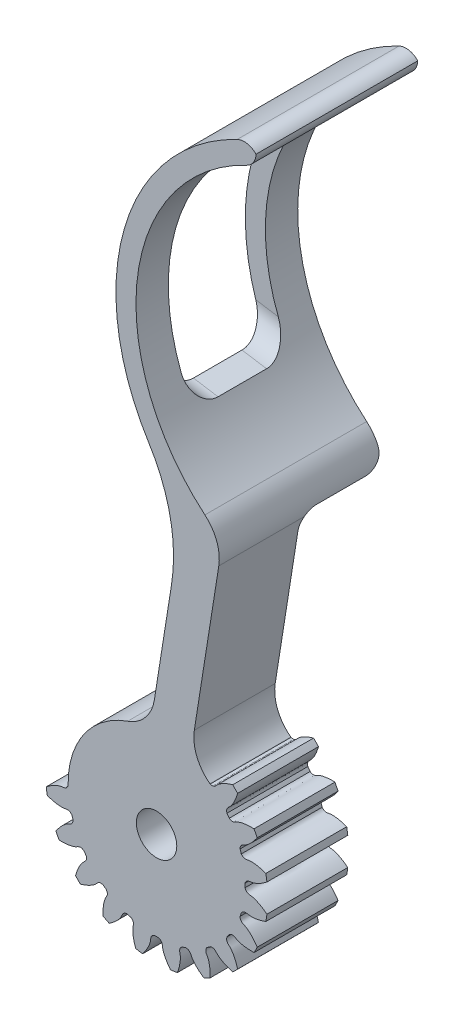
SolidWorks part; units mm, degrees
material "聚脂树脂"
ref_plane "前视基准面" through (0, 0, 0) normal (0, 0, 1) x (1, 0, 0)
ref_plane "上视基准面" through (0, 0, 0) normal (0, 1, 0) x (1, 0, 0)
ref_plane "右视基准面" through (0, 0, 0) normal (1, 0, 0) x (0, 0, -1)
other "Configuration Table"
sketch "草图1" plane through (0, 0, 0) normal (0, 0, 1) x (1, 0, 0)
  circle A0 centre (0, 0) radius 13.75
extrude "凸台-拉伸1" add sketch "草图1" along normal blind 10
ref_axis "基准轴1" through (0, 0, -1.5) along (0, 0, 1)
sketch "草图2" plane through (0, 0, 0) normal (0, 0, 1) x (1, 0, 0)
  line L0 (0, 0) -> (0, 13.75) construction
  circle A0 centre (0, 0) radius 13.75 construction
  arc A1 (0.2416, 10.9348) -> (-0.2416, 10.9348) centre (0, 0) ccw
  arc A2 (3.9764, 15.6228) -> (-3.9764, 15.6228) centre (0, 0) ccw
  spline S0 degree 3 poles (0.2416, 10.9348) (0.764, 11.1168) (0.6964, 11.4839) (0.7661, 11.8375) (0.7736, 11.8719) (0.7829, 11.9108) (0.7941, 11.954) (0.8075, 12.0015) (0.8231, 12.0532) (0.8413, 12.1091) (0.8621, 12.169) (0.8857, 12.2329) (0.9123, 12.3007) (0.9421, 12.3723) (0.9752, 12.4476) (1.0117, 12.5264) (1.0519, 12.6088) (1.0959, 12.6945) (1.1438, 12.7834) (1.1957, 12.8755) (1.2519, 12.9705) (1.3125, 13.0684) (1.3775, 13.1691) (1.4472, 13.2723) (1.5216, 13.3779) (1.601, 13.4858) (1.6853, 13.5958) (1.7747, 13.7078) (1.8694, 13.8216) (1.9693, 13.937) (2.0748, 14.0539) (2.1857, 14.1721) (2.3023, 14.2914) (2.4246, 14.4116) (2.5527, 14.5326) (2.6866, 14.6542) (2.8265, 14.7761) (2.9725, 14.8983) (3.1245, 15.0204) (3.2826, 15.1424) (3.4469, 15.2639) (3.6768, 15.427) (3.8549, 15.5454) (3.9764, 15.6228) knots 0 0 0 0 0.165916 0.170906 0.176664 0.183189 0.190482 0.198542 0.207371 0.216967 0.22733 0.238462 0.250361 0.263027 0.276462 0.290664 0.305634 0.321371 0.337876 0.355149 0.37319 0.391998 0.411574 0.431917 0.453028 0.474907 0.497554 0.520968 0.54515 0.570099 0.595817 0.622302 0.649554 0.677575 0.706363 0.735918 0.766242 0.797333 0.829191 0.861818 0.895212 0.929373 1 1 1 1
  spline S1 degree 3 poles (-0.2416, 10.9348) (-0.764, 11.1168) (-0.6964, 11.4839) (-0.7661, 11.8375) (-0.7736, 11.8719) (-0.7829, 11.9108) (-0.7941, 11.954) (-0.8075, 12.0015) (-0.8231, 12.0532) (-0.8413, 12.1091) (-0.8621, 12.169) (-0.8857, 12.2329) (-0.9123, 12.3007) (-0.9421, 12.3723) (-0.9752, 12.4476) (-1.0117, 12.5264) (-1.0519, 12.6088) (-1.0959, 12.6945) (-1.1438, 12.7834) (-1.1957, 12.8755) (-1.2519, 12.9705) (-1.3125, 13.0684) (-1.3775, 13.1691) (-1.4472, 13.2723) (-1.5216, 13.3779) (-1.601, 13.4858) (-1.6853, 13.5958) (-1.7747, 13.7078) (-1.8694, 13.8216) (-1.9693, 13.937) (-2.0748, 14.0539) (-2.1857, 14.1721) (-2.3023, 14.2914) (-2.4246, 14.4116) (-2.5527, 14.5326) (-2.6866, 14.6542) (-2.8265, 14.7761) (-2.9725, 14.8983) (-3.1245, 15.0204) (-3.2826, 15.1424) (-3.4469, 15.2639) (-3.6768, 15.427) (-3.8549, 15.5454) (-3.9764, 15.6228) knots 0 0 0 0 0.165916 0.170906 0.176664 0.183189 0.190482 0.198542 0.207371 0.216967 0.22733 0.238462 0.250361 0.263027 0.276462 0.290664 0.305634 0.321371 0.337876 0.355149 0.37319 0.391998 0.411574 0.431917 0.453028 0.474907 0.497554 0.520968 0.54515 0.570099 0.595817 0.622302 0.649554 0.677575 0.706363 0.735918 0.766242 0.797333 0.829191 0.861818 0.895212 0.929373 1 1 1 1
extrude "切除-拉伸1" cut sketch "草图2" along normal through all
pattern_circular "阵列(圆周)1" count 20 every 18 about axis through (0, 0, -1.5) along (0, 0, 1) of "切除-拉伸1"
sketch "草图6" plane through (0, 0, 0) normal (0, 0, -1) x (-1, 0, 0)
  line L0 (0, 0) -> (-10.311, 65.1009) construction
  line L1 (0, 0) -> (38.9643, 6.1713) construction
  line L2 (0, 0) -> (-30.4582, -4.8241) construction
  line L3 (-12.3461, -1.9554) -> (-21.1812, 53.827) construction
  line L4 (2.4692, 0.3911) -> (-3.2254, 36.3455)
  line L5 (-2.4692, -0.3911) -> (-8.1638, 35.5633)
  line L6 (-8.1638, 35.5633) -> (-14.2864, 74.2194)
  line L7 (-14.2864, 74.2194) -> (-21.4537, 55.5478) construction
  line L8 (-14.2864, 74.2194) -> (-7.9754, 90.6601) construction
  line L9 (-14.2864, 74.2194) -> (-11.9654, 80.2656)
  line L10 (-2.4692, -0.3911) -> (2.4692, 0.3911)
  circle A0 centre (0, 0) radius 12.5 construction
  circle A1 centre (-21.4537, 55.5478) radius 24 construction
  circle A2 centre (-21.4537, 55.5478) radius 26.4764 construction
  arc A3 (-11.9654, 80.2656) -> (-3.2254, 36.3455) centre (-21.4537, 55.5478) cw
  arc A4 (-12.8529, 77.9537) -> (-8.1638, 35.5633) centre (-21.4537, 55.5478) cw
  dimension "D1" = 25
  dimension "D4" = 48
  dimension "D5" = 30
  dimension "D2" = 5
  dimension "D3" = 58.22
extrude "凸台-拉伸2" add sketch "草图6" against normal blind 10 and the other way blind 10 contours A3 L9 L6 L5 L10 L4 | L5 | L4 region at (0.1292, 0.816, 0)
sketch "草图7" plane through (-2.4692, 0.3911, 0) normal (0.9877, -0.1564, 0) x (0, 0, -1)
  line L0 (0, 0) -> (0, 34)
  line L1 (0, 34) -> (10, 34)
  line L3 (10, 34) -> (10, 0)
  line L4 (10, 0) -> (0, 0) construction
  line L5 (10, 0) -> (10, 36.4026) construction
  line L6 (10, 0) -> (0, 0)
  line L7 (-5, 4.6588) -> (-5, 27.3083) construction
  line L8 (-10, 4.6588) -> (0, 4.6588) construction
  line L9 (-20, 34) -> (-20, 0)
  line L10 (-10, 34) -> (-20, 34)
  line L11 (-10, 0) -> (-10, 34)
  line L12 (-20, 0) -> (-10, 0)
  dimension "D1" = 34
extrude "切除-拉伸3" cut sketch "草图7" against normal blind 32 and the other way blind 10
ref_plane "基准面1" through (12.5, 0, 0) normal (1, 0, 0) x (0, 0, -1)
ref_axis "基准轴2" through (0, 0, -6) along (0, 0, 1)
ref_plane "基准面2" through (0, 0, 0) normal (-0.9877, 0.1564, 0) x (0, 0, 1)
ref_plane "基准面3" through (12.3461, -1.9554, 0) normal (-0.9877, 0.1564, 0) x (0, 0, 1)
fillet "圆角2" radius 2 2 edges at (5.3188, 33.5814, 0) (5.3188, 33.5814, -10)
sketch "草图16" plane through (0, 0, 10) normal (0, 0, 1) x (1, 0, 0)
  circle A0 centre (0, 0) radius 2.5
  dimension "D1" = 5
extrude "切除-拉伸5" cut sketch "草图16" against normal blind 16.5
sketch "草图19" plane through (0, 0, 0) normal (0, 0, -1) x (-1, 0, 0)
  circle A0 centre (0, 0) radius 8
  dimension "D1" = 16
extrude "切除-拉伸7" cut sketch "草图19" against normal blind 3.4
sketch "草图20" plane through (0, 0, 0) normal (0, 0, -1) x (-1, 0, 0)
  line L0 (0, 0) -> (3.6089, 10.325)
  line L1 (3.6089, 10.325) -> (7.1451, 20.4421)
  line L2 (0, 0) -> (10.9348, -0.2416)
  line L3 (10.9348, -0.2416) -> (20.7519, -0.2416)
  circle A0 centre (0, 0) radius 17.5
  circle A1 centre (0, 0) radius 10.9375
  arc A2 (-8.7044, 6.6228) -> (-8.9885, 6.2318) centre (0, 0) ccw construction
  dimension "D1" = 35
extrude "切除-拉伸8" cut sketch "草图20" against normal blind 10 contours A1 L3 A0 L1 region at (-11.1082, 7.7459, 0)
fillet "圆角3" radius 20 1 edges at (3.2254, 36.3455, 0)
fillet "圆角4" radius 5 1 edges at (8.1638, 35.5633, 0)
fillet "圆角5" radius 2 2 edges at (12.8529, 77.9537, 0) (11.9654, 80.2656, 0)
sketch "草图22" plane through (12.3461, -1.9554, 0) normal (-0.9877, 0.1564, 0) x (0, 0, 1)
  line L0 (5, -1.9493) -> (5, 109.7629) construction
  line L1 (10, -1.9493) -> (0, -1.9493) construction
  line L5 (-6, 43.22) -> (6, 43.22)
  line L6 (-6, 43.22) -> (-6, 73.22)
  line L7 (-6, 73.22) -> (6, 73.22)
  line L8 (6, 43.22) -> (6, 73.22)
  line L9 (-6, 43.22) -> (6, 73.22) construction
  line L10 (-6, 73.22) -> (6, 43.22) construction
  line L11 (-10, 79.9909) -> (-10, 40.8001) construction
  point P4 (0, 58.22)
  dimension "D1" = 58.22
  dimension "D2" = 12
  dimension "D3" = 30
  dimension "D4" = 4
extrude "切除-拉伸9" cut sketch "草图22" along normal blind 45
fillet "圆角6" radius 3 4 edges at (-0.9194, 43.9044, 6) (-0.9194, 43.9044, -6) (3.7737, 73.535, -6) (3.7737, 73.535, 6)
sketch "草图23" plane through (0, 0, 10) normal (0, 0, 1) x (1, 0, 0)
  line L0 (-0.7142, 11.472) -> (-0.8035, 10.9079)
  line L1 (1.8548, 27.6921) -> (-0.7142, 11.472) construction
  line L2 (4.2243, 10.6898) -> (4.1349, 10.1258)
  line L3 (7.6942, 32.5983) -> (4.2243, 10.6898) construction
  circle A0 centre (0, 0) radius 10.9375
  arc A1 (-1.7221, 13.6417) -> (-2.5777, 13.5062) centre (0, 0) ccw construction
  arc A2 (-1.7221, 13.6417) -> (-2.5777, 13.5062) centre (0, 0) ccw
  arc A3 (6.6252, 12.0486) -> (5.8534, 12.4419) centre (0, 0) ccw construction
  arc A4 (6.6252, 12.0486) -> (5.8534, 12.4419) centre (0, 0) ccw
  spline S0 degree 3 poles (1994.295, 137.7537) (-128.5862, -24.5238) (-16.3079, 32.6766) (-1.5748, 13.4516) (-1.4488, 13.2768) (-1.314, 13.073) (-1.1971, 12.8801) (-1.0972, 12.6991) (-1.0129, 12.531) (-0.9432, 12.3769) (-0.8867, 12.2375) (-0.8483, 12.1307) (-0.8181, 12.0376) (-0.7986, 11.9714) (-0.7799, 11.8994) (-0.7687, 11.8506) (0.1616, 7.1353) (-24.3178, -2.2468) (1928.686, 537.5875) knots -11.303789 -11.303789 -11.303789 -11.303789 0.502446 0.525093 0.568083 0.608002 0.644851 0.678629 0.709336 0.736973 0.761538 0.783033 0.792629 0.809518 0.816811 0.829094 0.834084 3.172509 3.172509 3.172509 3.172509 only from (-1.7221, 13.6417) to (-0.7142, 11.472) construction
  spline S1 degree 3 poles (-2000.7324, -84.7349) (23.8247, 5.3776) (-2.3586, 6.7359) (-2.931, 11.5081) (-2.9354, 11.558) (-2.9398, 11.6323) (-2.9424, 11.7223) (-2.941, 11.8445) (-2.9339, 11.9853) (-2.9194, 12.1444) (-2.8961, 12.3215) (-2.8626, 12.516) (-2.8175, 12.7274) (-2.7593, 12.9551) (-2.6999, 13.1539) (-2.6447, 13.3205) (5.4121, 36.1167) (129.8707, 16.4119) (-1939.2458, -485.2572) knots -2.172632 -2.172632 -2.172632 -2.172632 0.165916 0.170906 0.183189 0.190482 0.207371 0.22733 0.250361 0.276462 0.305634 0.337876 0.37319 0.411574 0.453028 0.474907 0.497554 12.30377 12.30377 12.30377 12.30377 only from (-3.1492, 10.4743) to (-2.5777, 13.5062) construction
  spline S2 degree 3 poles (-1.7221, 13.6417) (-1.653, 13.5549) (-1.5348, 13.399) (-1.3791, 13.1737) (-1.2534, 12.9751) (-1.1451, 12.788) (-1.0532, 12.6134) (-0.9763, 12.4522) (-0.9134, 12.3053) (-0.87, 12.1919) (-0.8354, 12.092) (-0.8128, 12.0203) (-0.7941, 11.954) (-0.7799, 11.8994) (-0.7687, 11.8506) (-0.74, 11.7051) (-0.733, 11.5811) (-0.7142, 11.472) knots 0.492568 0.492568 0.492568 0.492568 0.546972 0.588426 0.62681 0.662124 0.694366 0.723538 0.749639 0.77267 0.783033 0.801458 0.809518 0.816811 0.829094 0.834084 0.889499 0.889499 0.889499 0.889499
  spline S3 degree 3 poles (-3.1492, 10.4743) (-2.7087, 10.8088) (-2.8864, 11.137) (-2.931, 11.5081) (-2.9354, 11.558) (-2.9398, 11.6323) (-2.9424, 11.7223) (-2.941, 11.8445) (-2.9339, 11.9853) (-2.9194, 12.1444) (-2.8961, 12.3215) (-2.8626, 12.516) (-2.8175, 12.7274) (-2.7593, 12.9551) (-2.6866, 13.1982) (-2.6232, 13.3832) (-2.5848, 13.4873) (-2.5777, 13.5062) knots 0 0 0 0 0.165916 0.170906 0.183189 0.190482 0.207371 0.22733 0.250361 0.276462 0.305634 0.337876 0.37319 0.411574 0.453028 0.497554 0.507432 0.507432 0.507432 0.507432
  spline S4 degree 3 poles (1694.4124, -1060.787) (-118.4443, 55.7411) (6.0134, 36.0216) (6.6326, 11.8082) (6.6318, 11.5928) (6.6211, 11.3487) (6.6022, 11.1239) (6.5767, 10.9187) (6.5461, 10.7332) (6.5119, 10.5675) (6.4757, 10.4216) (6.4439, 10.3125) (6.4137, 10.2194) (6.3905, 10.1545) (6.3633, 10.0853) (6.3437, 10.0391) (4.3246, 5.6774) (-20.9966, 12.4766) (1876.592, -698.8356) knots -11.303841 -11.303841 -11.303841 -11.303841 0.502446 0.525093 0.568083 0.608002 0.644851 0.678629 0.709336 0.736973 0.761538 0.783033 0.792629 0.809518 0.816811 0.829094 0.834084 3.172618 3.172618 3.172618 3.172618 only from (6.6252, 12.0486) to (6.2318, 8.9885) construction
  spline S5 degree 3 poles (-1668.1553, 1107.2659) (22.4332, -9.6514) (2.0512, 6.836) (4.3931, 11.033) (4.4189, 11.076) (4.4589, 11.1387) (4.5098, 11.2131) (4.5827, 11.3111) (4.6712, 11.4208) (4.7765, 11.541) (4.8994, 11.6706) (5.0408, 11.8083) (5.2016, 11.9528) (5.3825, 12.1027) (5.5474, 12.2287) (5.6899, 12.331) (25.6075, 26.0379) (114.7154, -63.0598) (-1854.1489, 747.2949) knots -2.172504 -2.172504 -2.172504 -2.172504 0.165916 0.170906 0.183189 0.190482 0.207371 0.22733 0.250361 0.276462 0.305634 0.337876 0.37319 0.411574 0.453028 0.474907 0.497554 12.303849 12.303849 12.303849 12.303849 only from (4.2243, 10.6898) to (5.8534, 12.4419) construction
  spline S6 degree 3 poles (6.6252, 12.0486) (6.6301, 11.9377) (6.6341, 11.7422) (6.6276, 11.4683) (6.6126, 11.2338) (6.5902, 11.0188) (6.5619, 10.8235) (6.5293, 10.6479) (6.4939, 10.4921) (6.4623, 10.3749) (6.4317, 10.2737) (6.4078, 10.2024) (6.3839, 10.1378) (6.3633, 10.0853) (6.3437, 10.0391) (6.1867, 9.7) (5.9162, 9.4428) (6.2318, 8.9885) knots 0.492568 0.492568 0.492568 0.492568 0.546972 0.588426 0.62681 0.662124 0.694366 0.723538 0.749639 0.77267 0.783033 0.801458 0.809518 0.816811 0.829094 0.834084 1 1 1 1
  spline S7 degree 3 poles (4.2243, 10.6898) (4.2759, 10.7877) (4.3208, 10.9035) (4.3931, 11.033) (4.4189, 11.076) (4.4589, 11.1387) (4.5098, 11.2131) (4.5827, 11.3111) (4.6712, 11.4208) (4.7765, 11.541) (4.8994, 11.6706) (5.0408, 11.8083) (5.2016, 11.9528) (5.3825, 12.1027) (5.5842, 12.2567) (5.7442, 12.3691) (5.8366, 12.4308) (5.8534, 12.4419) knots 0.110501 0.110501 0.110501 0.110501 0.165916 0.170906 0.183189 0.190482 0.207371 0.22733 0.250361 0.276462 0.305634 0.337876 0.37319 0.411574 0.453028 0.497554 0.507432 0.507432 0.507432 0.507432
extrude "切除-拉伸10" cut sketch "草图23" against normal blind 10 contours S3 A0 L0 S2 A2 | S7 L2 A0 S6 A4 region at (-1.9252, 12.0147, 10) region at (5.5438, 10.8317, 10)
fillet "圆角7" radius 5 2 edges at (4.1349, 10.1258, 5) (-0.8035, 10.9079, 5)
